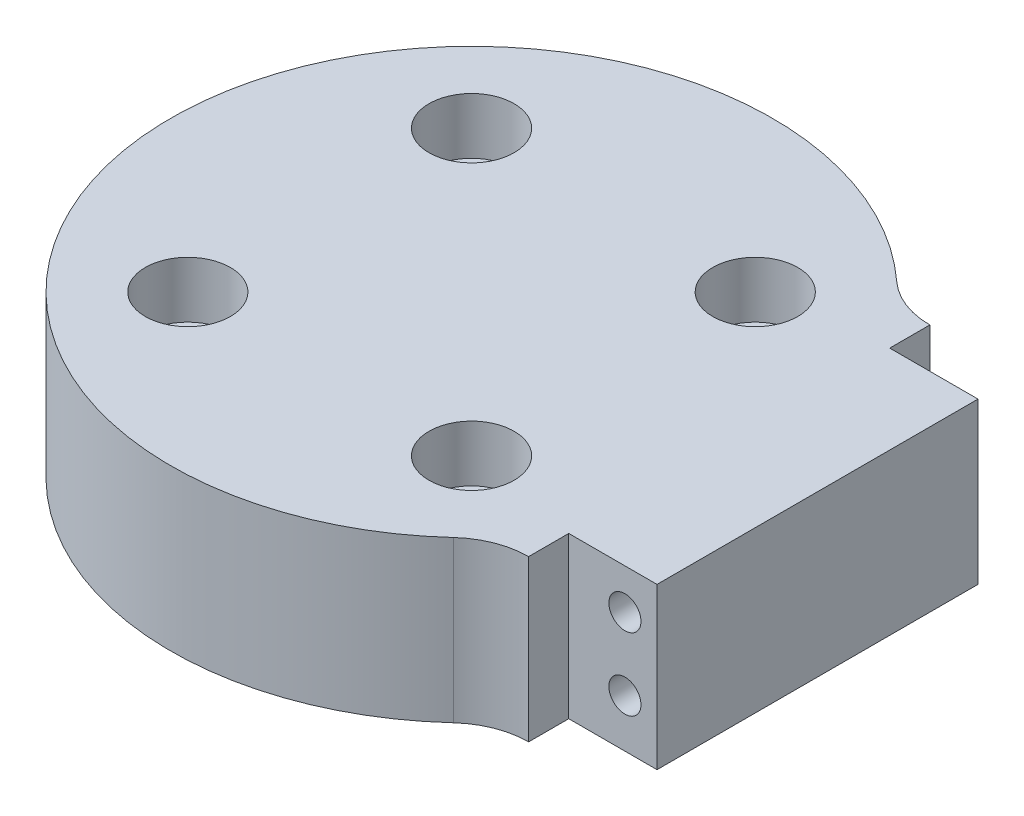
SolidWorks part; units mm, degrees
note: The reader was unsure of these and kept them because the rebuilt part matched: shared geometry of "Sketch13<3>", "Sketch16<3>".
ref_plane "Front Plane" through (0, 0, 0) normal (0, 0, 1) x (1, 0, 0)
ref_plane "Top Plane" through (0, 0, 0) normal (0, 1, 0) x (1, 0, 0)
ref_plane "Right Plane" through (0, 0, 0) normal (1, 0, 0) x (0, 0, -1)
sketch "Sketch1" plane through (0, 0, 0) normal (0, 1, 0) x (1, 0, 0)
  line L1 (-25, 25) -> (25, 25)
  line L2 (-25, 25) -> (-25, -25)
  line L3 (-25, -25) -> (25, -25)
  line L4 (25, 25) -> (25, -25)
  line L5 (-25, 25) -> (25, -25) construction
  line L6 (-25, -25) -> (25, 25) construction
  ellipse E0 centre (0, 0) end of major axis (19.7, 0) minor radius 19.1
  dimension "D1" = 39.4
  dimension "D2" = 38.2
  dimension "D3" = 50
  dimension "D4" = 50
extrude "Boss-Extrude1" add sketch "Sketch1" along normal blind 35
sketch "Sketch2" plane through (0, 35, 0) normal (0, 1, 0) x (1, 0, 0)
  line L0 (25, 25) -> (-25, 25) construction
  line L1 (-5, 25) -> (25, 25)
  line L2 (-5, 25) -> (-5, -25)
  line L3 (-5, -25) -> (25, -25)
  line L4 (25, 25) -> (25, -25)
  dimension "D1" = 30
extrude "Cut-Extrude1" cut sketch "Sketch2" against normal blind 35
sketch "Sketch3" plane through (0, 35, 0) normal (0, 1, 0) x (1, 0, 0)
  line L0 (-25, -25) -> (-5, -25) construction
  line L1 (-25, 25) -> (-12, 25)
  line L2 (-25, 25) -> (-25, -25)
  line L3 (-25, -25) -> (-12, -25)
  line L4 (-12, 25) -> (-12, -25)
  dimension "D1" = 13
extrude "Boss-Extrude2" add sketch "Sketch3" along normal blind 20
sketch "Sketch4" plane through (-25, 0, 0) normal (-1, 0, 0) x (0, 0, 1)
  line L4 (18.4746, 0) -> (18.4746, 35)
  line L5 (-18.4746, 0) -> (18.4746, 0)
  line L6 (-18.4746, 35) -> (-18.4746, 0)
  line L7 (-15.1475, 35) -> (-18.4746, 35)
  line L8 (18.4746, 0) -> (18.4746, 35)
  line L9 (-18.4746, 0) -> (18.4746, 0)
  line L10 (-18.4746, 35) -> (-18.4746, 0)
  line L11 (-15.1475, 35) -> (-18.4746, 35)
  line L14 (15.1475, 35) -> (-15.1475, 35)
  line L16 (15.1475, 35) -> (-15.1475, 35)
  line L18 (18.4746, 35) -> (15.1475, 35)
  line L20 (18.4746, 35) -> (15.1475, 35)
  circle A0 centre (18.4746, 50) radius 1.5
  dimension "D3" = 3
  dimension "D1" = 0
extrude "Cut-Extrude2" cut sketch "Sketch4" against normal through all contours A0
ref_plane "Plane1" through (-12, 55, -25) normal (-1, 0, 0) x (0, 0, 1)
sketch "Sketch5" plane through (-12, 55, -25) normal (-1, 0, 0) x (0, 0, 1)
  line L1 (0, 0) -> (36.9746, 0)
  line L2 (0, 0) -> (0, -20)
  line L3 (0, -20) -> (36.9746, -20)
  line L4 (0, -55) -> (50, -55)
  line L5 (50, -55) -> (50, 0)
  line L6 (50, 0) -> (0, 0)
  line L7 (0, 0) -> (0, -55)
  line L8 (0, -55) -> (50, -55)
  line L9 (50, -55) -> (50, 0)
  line L11 (0, 0) -> (0, -55) construction
  line L12 (43.4746, -55) -> (43.4746, -20)
  line L13 (6.5254, -55) -> (43.4746, -55)
  line L14 (6.5254, -20) -> (6.5254, -55)
  line L15 (9.8525, -20) -> (6.5254, -20)
  line L16 (43.4746, -55) -> (43.4746, -20) construction
  line L17 (6.5254, -55) -> (43.4746, -55)
  line L18 (6.5254, -20) -> (6.5254, -55) construction
  line L19 (9.8525, -20) -> (6.5254, -20) construction
  line L20 (36.9746, 0) -> (36.9746, -20)
  line L24 (50, 0) -> (0, 0)
  line L27 (40.1475, -20) -> (9.8525, -20)
  line L28 (40.1475, -20) -> (9.8525, -20)
  line L29 (43.4746, -20) -> (40.1475, -20)
  line L30 (43.4746, -20) -> (40.1475, -20)
  circle A0 centre (43.4746, -5) radius 1.5 construction
  dimension "D3" = 6.5
  dimension "D1" = 0
  dimension "D2" = 0
extrude "Cut-Extrude3" cut sketch "Sketch5" along normal blind 20 contours L20 L1 L2 L3
sketch "Sketch6" plane through (-5, 0, 0) normal (1, 0, 0) x (0, 0, -1)
  line L0 (-25, 35) -> (-25, 0) construction
  line L1 (25, 0) -> (25, 35) construction
  line L2 (-39, 27.5) -> (-25, 27.5)
  line L3 (-39, 27.5) -> (-39, 7.5)
  line L4 (-39, 7.5) -> (-25, 7.5)
  line L5 (-25, 27.5) -> (-25, 7.5)
  line L6 (-39, 27.5) -> (-25, 7.5) construction
  line L7 (-39, 7.5) -> (-25, 27.5) construction
  line L8 (39, 7.5) -> (25, 7.5)
  line L9 (39, 7.5) -> (39, 27.5)
  line L10 (39, 27.5) -> (25, 27.5)
  line L11 (25, 7.5) -> (25, 27.5)
  line L12 (39, 7.5) -> (25, 27.5) construction
  line L13 (39, 27.5) -> (25, 7.5) construction
  line L14 (32, 17.5) -> (-26.1195, 17.5) construction
  circle A0 centre (32, 17.5) radius 3.25
  circle A1 centre (-32, 17.5) radius 3.25
  point P4 (-32, 17.5)
  point P9 (32, 17.5)
  point P17 (-25, 17.5)
  point P18 (-25, 17.5)
  point P19 (25, 17.5)
  point P20 (25, 17.5)
  dimension "D4" = 6.5
  dimension "D5" = 6.5
  dimension "D2" = 20
  dimension "D1" = 14
  dimension "D3" = 14
extrude "Boss-Extrude3" add sketch "Sketch6" along normal blind 4 and the other way blind 20
sketch "Sketch7" plane through (-25, 0, 0) normal (-1, 0, 0) x (0, 0, 1)
  circle A0 centre (-32, 17.5) radius 5.3
  circle A1 centre (32, 17.5) radius 5.3
  circle A2 centre (18.4746, 50) radius 3
  dimension "D1" = 10.6
  dimension "D2" = 10.6
  dimension "D3" = 6
extrude "Cut-Extrude4" cut sketch "Sketch7" against normal blind 6
sketch "Sketch8" plane through (0, 35, 0) normal (0, 1, 0) x (1, 0, 0)
  line L4 (-12, -11.9746) -> (-25, -11.9746)
  line L5 (-25, -11.9746) -> (-25, -25)
  line L6 (-25, -25) -> (-12, -25)
  line L7 (-12, -25) -> (-12, -11.9746)
  line L8 (-12, -11.9746) -> (-25, -11.9746)
  line L9 (-25, -11.9746) -> (-25, -25)
  line L10 (-25, -25) -> (-12, -25)
  line L11 (-12, -25) -> (-12, -11.9746)
  dimension "D1" = 0
extrude "Cut-Extrude5" cut sketch "Sketch8" along normal blind 30
fillet "Fillet6" radius 4 2 edges at (-5, 17.5, 25) (-5, 17.5, -25)
fillet "Fillet5" radius 10 4 edges at (-15, 7.5, 25) (-15, 27.5, 25) (-15, 27.5, -25) (-15, 7.5, -25)
sketch "Sketch9" plane through (-25, 0, 0) normal (-1, 0, 0) x (0, 0, 1)
  line L8 (39, 27.5) -> (34.6825, 27.5)
  line L9 (25, 35) -> (-25, 35)
  line L10 (-34.6825, 27.5) -> (-39, 27.5)
  line L11 (-39, 27.5) -> (-39, 7.5)
  line L12 (-39, 7.5) -> (-34.6825, 7.5)
  line L13 (-25, 0) -> (25, 0)
  line L14 (34.6825, 7.5) -> (39, 7.5)
  line L15 (39, 7.5) -> (39, 27.5)
  line L16 (39, 27.5) -> (34.6825, 27.5)
  line L17 (25, 35) -> (-25, 35)
  line L18 (-34.6825, 27.5) -> (-39, 27.5)
  line L19 (-39, 27.5) -> (-39, 7.5)
  line L20 (-39, 7.5) -> (-34.6825, 7.5)
  line L21 (-25, 0) -> (25, 0)
  line L22 (34.6825, 7.5) -> (39, 7.5)
  line L23 (39, 7.5) -> (39, 27.5)
  circle A0 centre (32, 17.5) radius 5.3 construction
  circle A1 centre (-32, 17.5) radius 5.3 construction
  circle A2 centre (32, 17.5) radius 5.3
  circle A3 centre (-32, 17.5) radius 5.3
  arc A4 (25, 35) -> (34.6825, 27.5) centre (34.6825, 37.5) ccw
  arc A5 (-34.6825, 27.5) -> (-25, 35) centre (-34.6825, 37.5) ccw
  arc A6 (-25, 0) -> (-34.6825, 7.5) centre (-34.6825, -2.5) ccw
  arc A7 (34.6825, 7.5) -> (25, 0) centre (34.6825, -2.5) ccw
  arc A8 (25, 35) -> (34.6825, 27.5) centre (34.6825, 37.5) ccw
  arc A9 (-34.6825, 27.5) -> (-25, 35) centre (-34.6825, 37.5) ccw
  arc A10 (-25, 0) -> (-34.6825, 7.5) centre (-34.6825, -2.5) ccw
  arc A11 (34.6825, 7.5) -> (25, 0) centre (34.6825, -2.5) ccw
  dimension "D1" = 0
extrude "Boss-Extrude4" add sketch "Sketch9" along normal blind 30
sketch "Sketch10" plane through (0, 35, 0) normal (0, 1, 0) x (1, 0, 0)
  line L5 (-55, -25) -> (-5, -25) construction
  line L6 (-55, 25) -> (-35, 25)
  line L7 (-55, 25) -> (-55, -25)
  line L8 (-55, -25) -> (-35, -25)
  line L9 (-35, 25) -> (-35, -25)
  dimension "D1" = 20
extrude "Boss-Extrude5" add sketch "Sketch10" along normal blind 45
fillet "Fillet7" radius 10 1 edges at (-35, 35, 0)
sketch "Sketch11" plane through (-55, 0, 0) normal (-1, 0, 0) x (0, 0, 1)
  line L5 (25, 80) -> (25, 35) construction
  line L6 (-25, 80) -> (25, 80)
  line L7 (-25, 80) -> (-25, 60)
  line L8 (-25, 60) -> (25, 60)
  line L9 (25, 80) -> (25, 60)
  dimension "D1" = 20
extrude "Boss-Extrude6" add sketch "Sketch11" along normal blind 85
fillet "Fillet8" radius 9.5 1 edges at (-55, 60, 0)
sketch "Sketch13" plane through (0, 80, 0) normal (0, 1, 0) x (1, 0, 0)
  line L0 (-65, 25) -> (-65, -25) construction
  line L1 (-35, 25) -> (-140, 25) construction
  line L3 (-140, -25) -> (-35, -25) construction
  line L4 (-65, 0) -> (-140, 0) construction
  line L5 (-140, 25) -> (-124.372, 30.4609)
  line L6 (-140, 25) -> (-140, -25)
  line L7 (-140, -25) -> (-130.4508, -25)
  line L8 (-140, -25) -> (-140, 25) construction
  circle A0 centre (-102.5, 0) radius 37.5
  point P19 (-140, 0)
  dimension "D2" = 75
  dimension "D1" = 75
extrude "Boss-Extrude7" add sketch "Sketch13" against normal up to surface (20 mm away) up to face at (-102.25, 60, 0)
extrude "Cut-Extrude6" cut sketch "Sketch13<3>" against normal blind 85
sketch "Sketch13<3>" plane through (0, 80, 0) normal (0, 1, 0) x (1, 0, 0) same geometry as "Sketch13"
fillet "Fillet9" radius 10 2 edges at (-74.5492, 70, -25) (-74.5492, 70, 25)
fillet "Fillet10" radius 10 1 edges at (-35, 80, 0)
sketch "Sketch14" plane through (0, 80, 0) normal (0, 1, 0) x (1, 0, 0)
  line L0 (-102.5, 25) -> (-102.5, -25) construction
  line L1 (-102.5, -25) -> (-77.5, 0) construction
  line L2 (-77.5, 0) -> (-102.5, 25) construction
  line L3 (-102.5, 25) -> (-127.5, 0) construction
  line L4 (-127.5, 0) -> (-77.5, 0) construction
  line L5 (-127.5, 0) -> (-102.5, -25) construction
  line L6 (-120.1777, -17.6777) -> (-84.8223, 17.6777) construction
  line L7 (-120.1777, 17.6777) -> (-84.8223, -17.6777) construction
  circle A0 centre (-102.5, 0) radius 25 construction
  circle A1 centre (-120.1777, 17.6777) radius 3.25
  circle A2 centre (-120.1777, -17.6777) radius 3.25
  circle A3 centre (-84.8223, -17.6777) radius 3.25
  circle A4 centre (-84.8223, 17.6777) radius 3.25
  point P10 (-102.5, 0)
  point P13 (-102.5, 0)
  dimension "D4" = 6.5
  dimension "D5" = 6.5
  dimension "D1" = 50
  dimension "D2" = 6.5
  dimension "D3" = 6.5
extrude "Cut-Extrude7" cut sketch "Sketch14" against normal blind 85
sketch "Sketch15" plane through (0, 80, 0) normal (0, 1, 0) x (1, 0, 0)
  circle A0 centre (-120.1777, 17.6777) radius 5.3
  circle A1 centre (-120.1777, -17.6777) radius 5.3
  circle A2 centre (-84.8223, -17.6777) radius 5.3
  circle A3 centre (-84.8223, 17.6777) radius 5.3
  dimension "D1" = 10.6
  dimension "D2" = 10.6
  dimension "D3" = 10.6
  dimension "D4" = 10.6
extrude "Cut-Extrude8" cut sketch "Sketch15" against normal blind 7
sketch "Sketch16" plane through (-55, 0, 0) normal (-1, 0, 0) x (0, 0, 1)
  line L1 (-25.9378, 17.5) -> (-28.9689, 22.75)
  line L2 (-28.9689, 22.75) -> (-35.0311, 22.75)
  line L3 (-35.0311, 22.75) -> (-38.0622, 17.5)
  line L4 (-38.0622, 17.5) -> (-35.0311, 12.25)
  line L5 (-35.0311, 12.25) -> (-28.9689, 12.25)
  line L6 (-28.9689, 12.25) -> (-25.9378, 17.5)
  line L7 (25.9378, 17.5) -> (28.9689, 12.25)
  line L8 (28.9689, 12.25) -> (35.0311, 12.25)
  line L9 (35.0311, 12.25) -> (38.0622, 17.5)
  line L10 (38.0622, 17.5) -> (35.0311, 22.75)
  line L11 (35.0311, 22.75) -> (28.9689, 22.75)
  line L12 (28.9689, 22.75) -> (25.9378, 17.5)
  circle A0 centre (-32, 17.5) radius 5.25 construction
  circle A1 centre (32, 17.5) radius 5.25 construction
  circle A2 centre (32, 17.5) radius 3.25 construction
  circle A3 centre (-32, 17.5) radius 3.25 construction
  circle A4 centre (32, 17.5) radius 3.25
  circle A5 centre (-32, 17.5) radius 3.25
  dimension "D1" = 10.5
  dimension "D2" = 10.5
extrude "Boss-Extrude9" add sketch "Sketch16" against normal up to surface (36 mm away) up to face at (-19, 17.5, -26.7)
extrude "Cut-Extrude11" cut sketch "Sketch16<3>" against normal blind 10
sketch "Sketch16<3>" plane through (-55, 0, 0) normal (-1, 0, 0) x (0, 0, 1) same geometry as "Sketch16"
sketch "Sketch18" plane through (-1, 0, 0) normal (1, 0, 0) x (0, 0, -1)
  line L1 (-39, 0) -> (39, 0)
  line L2 (-39, 0) -> (-39, 80)
  line L3 (-39, 80) -> (39, 80)
  line L4 (39, 0) -> (39, 80)
extrude "Cut-Extrude13" cut sketch "Sketch18" against normal up to vertex (69.3869 mm away) up to point (-70.3869, 60, 25)
sketch "Sketch19" plane through (-70.3869, 0, 0) normal (1, 0, 0) x (0, 0, -1)
  line L0 (25, 80) -> (-25, 80) construction
  line L1 (-20, 80) -> (20, 80)
  line L2 (-20, 80) -> (-20, 60)
  line L3 (-20, 60) -> (20, 60)
  line L4 (20, 80) -> (20, 60)
  line L5 (25, 60) -> (-25, 60) construction
  line L6 (-25, 80) -> (-25, 60) construction
  dimension "D1" = 40
  dimension "D2" = 5
extrude "Boss-Extrude10" add sketch "Sketch19" along normal blind 11
sketch "Sketch20" plane through (0, 0, 20) normal (0, 0, 1) x (1, 0, 0)
  line L1 (-59.3869, 80) -> (-70.3869, 80) construction
  line L3 (-59.3869, 80) -> (-59.3869, 60) construction
  circle A0 centre (-63.3869, 75) radius 2
  circle A1 centre (-63.3869, 66) radius 2
  point P8 (0, 0)
  dimension "D1" = 4
  dimension "D2" = 4
  dimension "D3" = 5
  dimension "D4" = 9
sketch "Sketch21" plane through (0, 0, -20) normal (0, 0, -1) x (-1, 0, 0)
  line L1 (59.3869, 80) -> (70.3869, 80) construction
  line L3 (59.3869, 60) -> (59.3869, 80) construction
  circle A0 centre (63.3869, 75) radius 2
  circle A1 centre (63.3869, 66) radius 2
  point P6 (0, 0)
  dimension "D1" = 4
  dimension "D3" = 5
  dimension "D2" = 4
  dimension "D4" = 9
extrude "Cut-Extrude14" cut sketch "Sketch20" against normal blind 9
extrude "Cut-Extrude15" cut sketch "Sketch21" against normal blind 9
equation "\"D3@Sketch6\"=\"D1@Sketch6\""
equation "\"D5@Sketch6\"=\"D4@Sketch6\""
equation "\"D2@Sketch7\"=\"D1@Sketch7\""
equation "\"D3@Sketch14\"=\"D2@Sketch14\""
equation "\"D4@Sketch14\"=\"D2@Sketch14\""
equation "\"D5@Sketch14\"=\"D2@Sketch14\""
equation "\"D3@Sketch15\"=\"D1@Sketch15\""
equation "\"D4@Sketch15\"=\"D1@Sketch15\""
equation "\"D2@Sketch15\"=\"D1@Sketch15\""
equation "\"D2@Sketch16\"=\"D1@Sketch16\""
